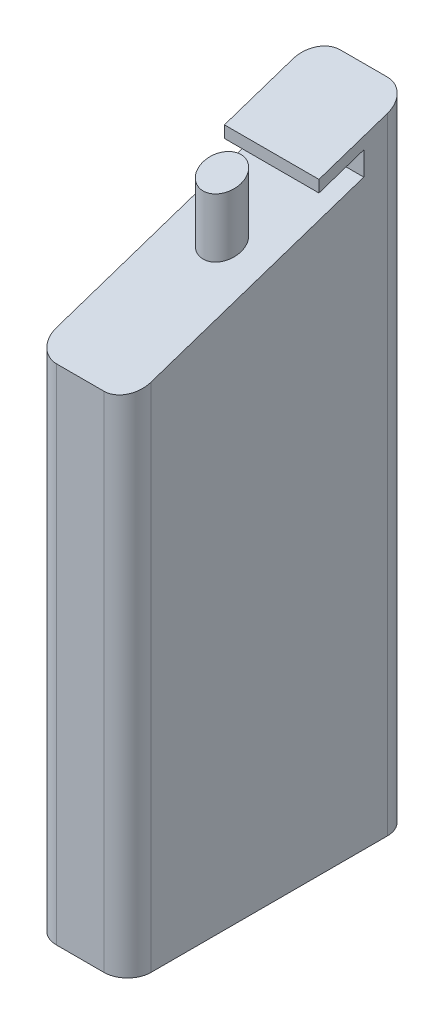
SolidWorks part; units mm, degrees
material "ABS"
ref_plane "Front Plane" through (0, 0, 0) normal (0, 0, 1) x (1, 0, 0)
ref_plane "Top Plane" through (0, 0, 0) normal (0, 1, 0) x (1, 0, 0)
ref_plane "Right Plane" through (0, 0, 0) normal (1, 0, 0) x (0, 0, -1)
sketch "Sketch1" plane through (0, 0, 0) normal (0, 1, 0) x (1, 0, 0)
  line L0 (-12.7, 25.4) -> (12.7, 25.4)
  line L1 (-12.7, -38.1) -> (12.7, -38.1)
  line L2 (-12.7, -38.1) -> (-12.7, 38.1)
  line L3 (-12.7, 38.1) -> (12.7, 38.1)
  line L4 (12.7, -38.1) -> (12.7, 38.1)
  line L5 (-12.7, -38.1) -> (12.7, 38.1) construction
  line L6 (-12.7, 38.1) -> (12.7, -38.1) construction
  point P0 (0, 0)
  dimension "D3" = 12.7
  dimension "D1" = 25.4
  dimension "D2" = 76.2
extrude "Boss-Extrude1" add sketch "Sketch1" along normal blind 160.782 contours L1 L4 L0 L2 | L0 L4 L3 L2 region at (0, 0, -31.75) region at (0, 0, 6.35)
sketch "Sketch4" plane through (12.7, 0, 0) normal (1, 0, 0) x (0, 0, -1)
  line L0 (38.1, 160.782) -> (-38.1, 160.782)
  line L1 (-38.1, 160.782) -> (-38.1, 135.2858)
  line L3 (-38.1, 135.2858) -> (38.1, 160.782)
  line L4 (-38.1, 135.2858) -> (38.1, 135.2858) construction
  line L7 (-38.1, 160.782) -> (-38.1, 0) construction
  line L8 (38.1, 160.782) -> (38.1, 0) construction
  dimension "D1" = 18.5
extrude "Cut-Extrude2" cut sketch "Sketch4" against normal through all both and the other way through all
sketch "Sketch5" plane through (0, 133.1295, 44.5445) normal (0, 0.9483, 0.3173) x (1, 0, 0)
  line L0 (0, 87.148) -> (0, 6.7957) construction
  line L1 (12.7, 87.148) -> (-12.7, 87.148) construction
  line L2 (-12.7, 6.7957) -> (12.7, 6.7957) construction
  line L3 (-12.7, 46.9719) -> (12.7, 46.9719) construction
  line L4 (-12.7, 6.7957) -> (-12.7, 87.148) construction
  line L5 (12.7, 87.148) -> (12.7, 6.7957) construction
  circle A0 centre (0, 46.9719) radius 3.175
  dimension "D1" = 6.35
extrude "Cut-Extrude3" [suppressed] cut sketch "Sketch5" against normal blind 6.35
ref_point "Point1" [suppressed]
extrude "Boss-Extrude2" add sketch "Sketch1<5>" along normal blind 9.525 from surface contours L0 L4 L3 L2 region at (0, 0, -31.75) starting at face at (-3.175, 151.2209, -9.525)
sketch "Sketch1<5>" plane through (0, 0, 0) normal (0, 1, 0) x (1, 0, 0) same geometry as "Sketch1"
sketch "Sketch8" plane through (0, 0, -25.4) normal (0, 0, 1) x (1, 0, 0)
  line L0 (12.7, 166.0576) -> (12.7, 156.5326) construction
  line L1 (-12.7, 166.0576) -> (12.7, 166.0576)
  line L2 (-12.7, 166.0576) -> (-12.7, 162.8826)
  line L3 (-12.7, 162.8826) -> (12.7, 162.8826)
  line L4 (12.7, 166.0576) -> (12.7, 162.8826)
  dimension "D1" = 3.175
extrude "Boss-Extrude3" add sketch "Sketch8" along direction (0, 0.3173, -0.9483) on the side of the normal blind 12.7
fillet "Fillet1" radius 6.35 4 edges at (-12.7, 85.1535, -38.1) (-12.7, 67.6429, 38.1) (12.7, 67.6429, 38.1)
sketch "Sketch9" plane through (0, 0, 0) normal (0, -1, 0) x (1, 0, 0)
  circle A0 centre (0, 0) radius 5.715
  circle A1 centre (0, 0) radius 5.08
  dimension "D1" = 11.43
  dimension "D2" = 10.16
extrude "Boss-Extrude4" add sketch "Sketch9" against normal blind 15.875 from surface contours A1 region at (0, 0, 0) starting at face at (0, 144.5232, 10.4925)
extrude "Cut-Extrude5" cut sketch "Sketch9<3>" against normal blind 15.875 contours A1 | A0 A1 region at (-5.5534, 0, 0) region at (0, 0, 0)
sketch "Sketch9<3>" plane through (0, 0, 0) normal (0, -1, 0) x (1, 0, 0) same geometry as "Sketch9"
ref_point "Point2"
